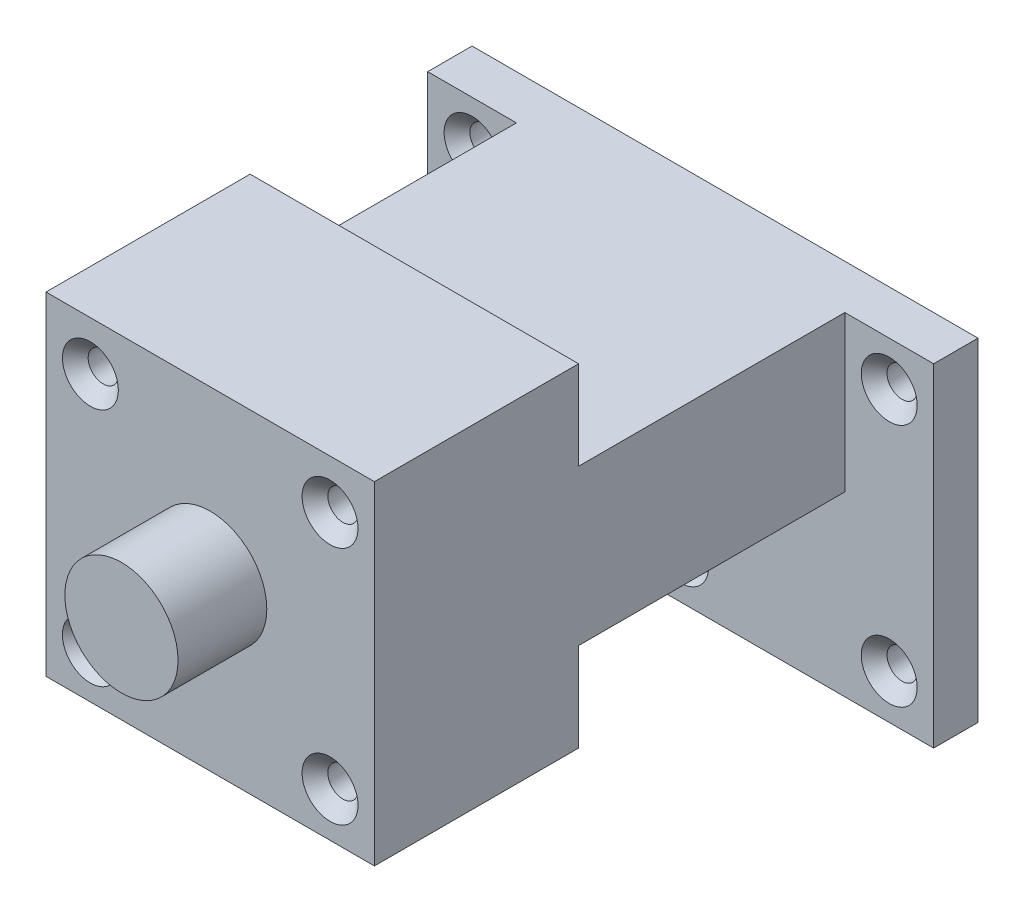
SolidWorks part; units mm, degrees
ref_plane "Plan de face" through (0, 0, 0) normal (0, 0, 1) x (1, 0, 0)
ref_plane "Plan de dessus" through (0, 0, 0) normal (0, 1, 0) x (1, 0, 0)
ref_plane "Plan de droite" through (0, 0, 0) normal (1, 0, 0) x (0, 0, -1)
sketch "Esquisse1" plane through (0, 0, 0) normal (0, 0, 1) x (1, 0, 0)
  line L2 (0, 0) -> (37, 0)
  line L3 (0, 0) -> (0, 37.5)
  line L4 (0, 37.5) -> (37, 37.5)
  line L5 (37, 0) -> (37, 37.5)
  dimension "D1" = 37.5
  dimension "D2" = 37
extrude "Boss.-Extru.1" add sketch "Esquisse1" along normal blind 58
sketch "Esquisse2" plane through (0, 0, 58) normal (0, 0, 1) x (1, 0, 0)
  line L0 (37, 0) -> (37, 37.5) construction
  line L4 (37, 37.5) -> (0, 37.5) construction
  circle A0 centre (18.5, 19) radius 6.375
  dimension "D3" = 12.75
  dimension "D1" = 18.5
  dimension "D2" = 18.5
extrude "Boss.-Extru.2" add sketch "Esquisse2" along normal blind 10
sketch "Esquisse3" plane through (0, 0, 58) normal (0, 0, 1) x (1, 0, 0)
  line L0 (37, 37.5) -> (0, 37.5) construction
  line L1 (0, 37.5) -> (0, 0) construction
  line L2 (37, 0) -> (37, 37.5) construction
  circle A0 centre (5, 32) radius 1.5
  circle A1 centre (32, 32) radius 1.5
  circle A2 centre (32, 5) radius 1.5
  circle A3 centre (5, 5) radius 1.5
  dimension "D3" = 3
  dimension "D5" = 3
  dimension "D9" = 3
  dimension "D11" = 3
  dimension "D1" = 5.5
  dimension "D2" = 5.5
  dimension "5" = 5
  dimension "D4" = 5
  dimension "D6" = 5
  dimension "D7" = 5
  dimension "D8" = 27
  dimension "D10" = 27
sketch "Esquisse6" plane through (0, 0, 0) normal (0, -1, 0) x (1, 0, 0)
  line L1 (0, 0) -> (10, 0)
  line L2 (0, 0) -> (0, 5)
  line L3 (0, 5) -> (10, 5)
  line L4 (10, 0) -> (10, 5)
  line L5 (37, 0) -> (27, 0)
  line L6 (37, 0) -> (37, 5)
  line L7 (37, 5) -> (27, 5)
  line L8 (27, 0) -> (27, 5)
  dimension "D1" = 10
  dimension "D2" = 5
  dimension "D3" = 10
  dimension "D4" = 5
extrude "Boss.-Extru.3" [suppressed] add sketch "Esquisse6" along normal blind 10
sketch "Esquisse7" plane through (0, 37.5, 0) normal (0, 1, 0) x (1, 0, 0)
  line L1 (0, 0) -> (10, 0)
  line L2 (0, 0) -> (0, -5)
  line L3 (0, -5) -> (10, -5)
  line L4 (10, 0) -> (10, -5)
  line L5 (37, 0) -> (27, 0)
  line L6 (37, 0) -> (37, -5)
  line L7 (37, -5) -> (27, -5)
  line L8 (27, 0) -> (27, -5)
  dimension "D1" = 5
  dimension "D2" = 5
  dimension "D3" = 10
  dimension "D4" = 10
extrude "Boss.-Extru.4" [suppressed] add sketch "Esquisse7" along normal blind 10
sketch "Esquisse8" [suppressed] plane through (0, 0, 5) normal (0, 0, 1) x (1, 0, 0)
  line L0 (37, -10) -> (27, -10) construction
  line L1 (37, -10) -> (37, 0) construction
  circle A0 centre (32, -5) radius 2.6226
  circle A1 centre (4.4036, -5.1811) radius 2.9344
  circle A2 centre (4.4036, 42.3532) radius 2.5459
  circle A3 centre (32.4325, 42.3532) radius 2.5419
  dimension "D1" = 5
  dimension "5" = 5
sketch "Esquisse10" plane through (0, 0, 0) normal (0, 0, -1) x (-1, 0, 0)
  line L0 (0, 37.5) -> (0, 0) construction
  line L1 (-37, 0) -> (-27, 0)
  line L2 (-37, 0) -> (-37, 10)
  line L3 (-37, 10) -> (-27, 10)
  line L4 (-27, 0) -> (-27, 10)
  line L5 (-37, 37.5) -> (0, 37.5)
  line L6 (-37, 37.5) -> (-37, 27.5)
  line L7 (-37, 27.5) -> (0, 27.5)
  line L8 (0, 37.5) -> (0, 27.5)
  line L13 (0, 0) -> (-10, 0)
  line L14 (0, 0) -> (0, 10)
  line L15 (0, 10) -> (-10, 10)
  line L16 (-10, 0) -> (-10, 10)
  dimension "D1" = 10
  dimension "D5" = 10
  dimension "D6" = 10
  dimension "10" = 10
  dimension "D7" = 10
extrude "Enlèv. mat.-Extru.1" cut sketch "Esquisse10" against normal blind 30 from offset 5 offset against normal yes
hole_wizard "Fraisage pour vis à tête fraisée bombée M31" positions "Esquisse4" profile "Esquisse5" countersink size "M3" standard "ISO"
sketch "Esquisse4" plane through (0, 0, 58) normal (0, 0, 1) x (1, 0, 0)
  point P0 (5, 32)
  point P3 (32, 32)
  point P6 (32, 5)
  point P9 (5, 5)
sketch "Esquisse5" plane through (5, 32, 58) normal (1, 0, 0) x (0, -1, 0)
  line L0 (0, 0) -> (0, 24.0215)
  line L1 (0, 24.0215) -> (1.7, 23)
  line L2 (1.7, 23) -> (1.7, 1.45)
  line L3 (1.7, 1.45) -> (3.15, 0)
  line L5 (3.15, 0) -> (0, 0)
  line L6 (-1.7, 1.45) -> (-3.15, 0) construction
  line L10 (0, 24.0215) -> (-1.7, 23) construction
  line L11 (0, -6.35) -> (0, 107.95) construction
  dimension "Diamètre du perçage" = 3.4
  dimension "Profondeur du perçage" = 23
  dimension "Diamètre du fraisage entrant" = 6.3
  dimension "Angle du fraisage entrant" = 90
  dimension "Angle de pointe" = 118
sketch "Esquisse11" plane through (0, 0, 0) normal (0, 0, -1) x (-1, 0, 0)
  line L8 (-37, 27.5) -> (0, 27.5) construction
  line L9 (-37, 27.5) -> (-47, 27.5)
  line L12 (-47, 27.5) -> (-47, -10)
  line L13 (0, 27.5) -> (10, 27.5)
  line L16 (10, 27.5) -> (10, -10)
  line L22 (-47, -10) -> (10, -10)
  line L23 (0, 0) -> (-37, 0) construction
  line L25 (-37, 0) -> (0, 0)
  line L26 (-37, 27.5) -> (-37, 0)
  line L28 (0, 27.5) -> (0, 0)
  dimension "D1" = 10
  dimension "D2" = 10
  dimension "D3" = 10
extrude "Boss.-Extru.5" add sketch "Esquisse11" against normal blind 5
sketch "Esquisse12" plane through (0, 0, 0) normal (0, 0, -1) x (-1, 0, 0)
  line L1 (-37, 37.5) -> (0, 37.5)
  line L2 (-37, 37.5) -> (-37, 27.5)
  line L3 (-37, 27.5) -> (0, 27.5)
  line L4 (0, 37.5) -> (0, 27.5)
extrude "Enlèv. mat.-Extru.2" cut sketch "Esquisse12" against normal up to surface (5 mm away) up to face at (18.5, 32.5, 5)
sketch "Esquisse13" plane through (0, 0, 5) normal (0, 0, 1) x (1, 0, 0)
  line L0 (-10, 27.5) -> (0, 27.5) construction
  line L1 (-10, -10) -> (-10, 27.5) construction
  line L2 (47, -10) -> (-10, -10) construction
  line L3 (47, 27.5) -> (47, -10) construction
  line L6 (37, 27.5) -> (47, 27.5) construction
  circle A0 centre (-5, 22.5) radius 1.5
  circle A1 centre (-5, -5) radius 1.5
  circle A2 centre (18.5, -5) radius 1.5
  circle A3 centre (42, -5) radius 1.5
  circle A4 centre (42, 22.5) radius 1.5
  dimension "D5" = 3
  dimension "D6" = 3
  dimension "D9" = 3
  dimension "D12" = 3
  dimension "D15" = 3
  dimension "D1" = 5
  dimension "D2" = 5
  dimension "D3" = 5
  dimension "D4" = 5
  dimension "D7" = 5
  dimension "D8" = 28.5
  dimension "D10" = 5
  dimension "D11" = 5
  dimension "D13" = 5
  dimension "D14" = 5
hole_wizard "Fraisage pour vis à tête fraisée bombée M32" positions "Esquisse14" profile "Esquisse15" countersink size "M3" standard "ISO"
sketch "Esquisse14" plane through (0, 0, 5) normal (0, 0, 1) x (1, 0, 0)
  point P0 (-5, 22.5)
  point P3 (-5, -5)
  point P6 (18.5, -5)
  point P9 (42, -5)
  point P12 (42, 22.5)
sketch "Esquisse15" plane through (-5, 22.5, 5) normal (1, 0, 0) x (0, -1, 0)
  line L0 (0, 0) -> (0, 6.0215)
  line L1 (0, 6.0215) -> (1.7, 5)
  line L2 (1.7, 5) -> (1.7, 1.45)
  line L3 (1.7, 1.45) -> (3.15, 0)
  line L5 (3.15, 0) -> (0, 0)
  line L6 (-1.7, 1.45) -> (-3.15, 0) construction
  line L10 (0, 6.0215) -> (-1.7, 5) construction
  line L11 (0, -6.35) -> (0, 107.95) construction
  dimension "Diamètre du perçage" = 3.4
  dimension "Profondeur du perçage" = 5
  dimension "Diamètre du fraisage entrant" = 6.3
  dimension "Angle du fraisage entrant" = 90
  dimension "Angle de pointe" = 118
